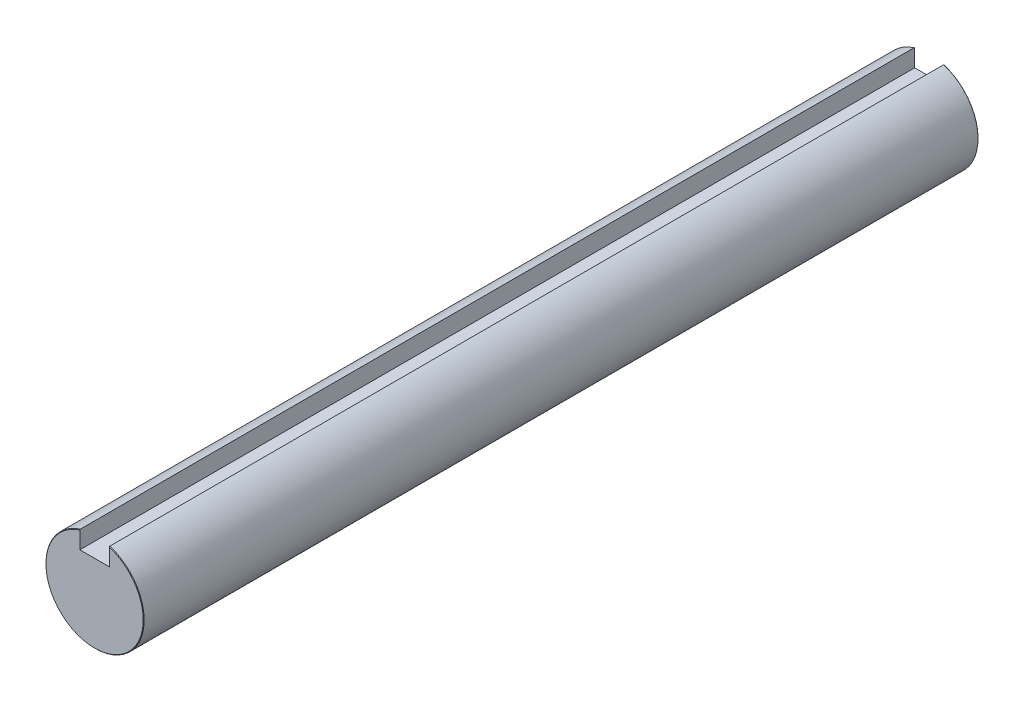
SolidWorks part; units mm, degrees
ref_plane "Front Plane" through (0, 0, 0) normal (0, 0, 1) x (1, 0, 0)
ref_plane "Top Plane" through (0, 0, 0) normal (0, 1, 0) x (1, 0, 0)
ref_plane "Right Plane" through (0, 0, 0) normal (1, 0, 0) x (0, 0, -1)
sketch "Sketch1" plane through (0, 0, 0) normal (1, 0, 0) x (0, 0, -1)
  line L0 (0, 0) -> (0, 5) construction
  line L1 (-42.5, 5) -> (42.5, 5)
  line L2 (-42.5, 5) -> (-42.5, -5)
  line L3 (-42.5, -5) -> (42.5, -5)
  line L4 (42.5, 5) -> (42.5, -5)
  line L5 (-42.5, 5) -> (42.5, -5) construction
  line L6 (-42.5, -5) -> (42.5, 5) construction
  line L7 (0, 0) -> (0, -5) construction
  point P0 (0, 0)
  point P8 (-31, 5)
  point P10 (31, 5)
  point P11 (-27.1667, -5)
  point P12 (29.221, -5)
  dimension "Diameter" = 10
  dimension "Length" = 85
  dimension "D1" = 11.5
  dimension "D2" = 11.5
  dimension "Keyway Length" = 85
  dimension "D3" = 13.279
  dimension "D5" = 15.3333
sketch "Sketch2" plane through (0, 0, 0) normal (0, 0, 1) x (1, 0, 0)
  line L0 (0, 0) -> (0, 5) construction
  line L2 (1.5, 2.9697) -> (-1.5, 2.9697)
  line L3 (1.5, 2.9697) -> (1.5, 4.7697)
  line L4 (1.5, 4.7697) -> (-1.5, 4.7697)
  line L5 (-1.5, 2.9697) -> (-1.5, 4.7697)
  line L6 (1.5, 2.9697) -> (-1.5, 4.7697) construction
  line L7 (1.5, 4.7697) -> (-1.5, 2.9697) construction
  circle A0 centre (0, 0) radius 5
  point P3 (0, 3.8697)
  dimension "Keyway Width" = 3
  dimension "Keyway Depth" = 1.8
sketch "Sketch3" plane through (0, 0, 0) normal (0, 0, 1) x (1, 0, 0)
  line L1 (-1.5, 2.9697) -> (-1.5, 4.7697) construction
  line L2 (1.5, 2.9697) -> (-1.5, 2.9697) construction
  line L3 (1.5, 2.9697) -> (1.5, 4.7697) construction
  line L5 (-1.5, 2.9697) -> (-1.5, 4.7697)
  line L6 (1.5, 2.9697) -> (-1.5, 2.9697)
  line L7 (1.5, 2.9697) -> (1.5, 4.7697)
  circle A0 centre (0, 0) radius 5 construction
  arc A1 (-1.5, 4.7697) -> (1.5, 4.7697) centre (0, 0) ccw
extrude "Boss-Extrude1" add sketch "Sketch3" along normal up to vertex (42.5 mm away) and the other way up to vertex (42.5 mm away) up to point (0, 5, 42.5) other way up to point (0, 5, -42.5)
chamfer "Chamfer1" distance 0.05 angle 45 2 edges at (0, -5, 42.5) (0, -5, -42.5)
equation "\"D2@Sketch1\"=1.15*\"Diameter@Sketch1\""
equation "\"D1@Sketch1\"=\"D2@Sketch1\""
equation "\"D1@Chamfer1\"=\"Diameter@Sketch1\"*.005"
equation "\"D3@Sketch1\"=\"D2@Sketch1\"/(2*tan(.5236*180/pi))*4/3"
equation "\"D5@Sketch1\" = 4 / 3 * \"D2@Sketch1\""
